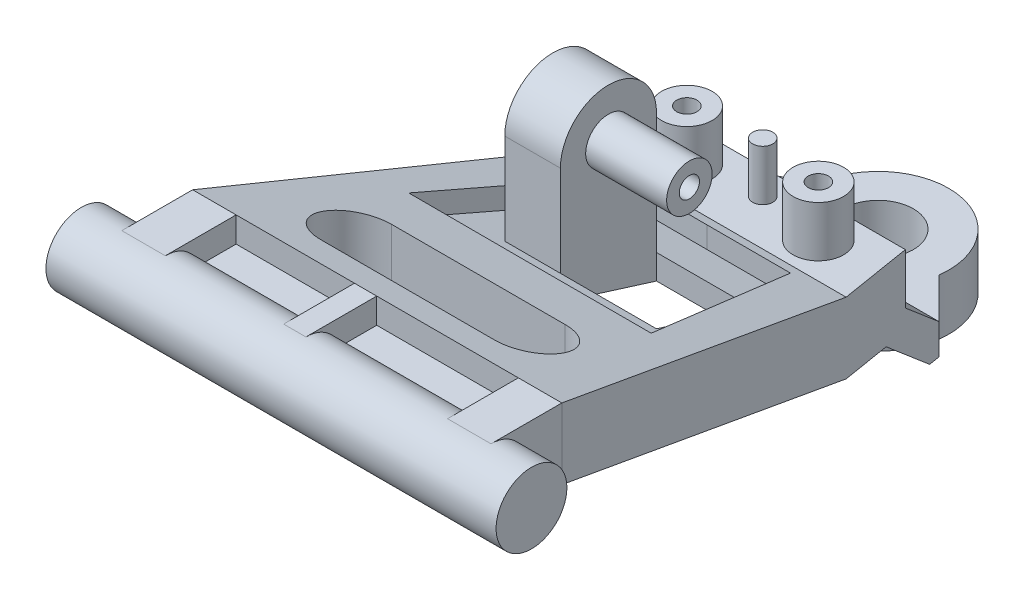
SolidWorks part; units mm, degrees
note: The reader was unsure of these and kept them because the rebuilt part matched: shared geometry of "Sketch13<3>", "Sketch13<4>".
ref_plane "Front Plane" through (0, 0, 0) normal (0, 0, 1) x (1, 0, 0)
ref_plane "Top Plane" through (0, 0, 0) normal (0, 1, 0) x (1, 0, 0)
ref_plane "Right Plane" through (0, 0, 0) normal (1, 0, 0) x (0, 0, -1)
sketch "Sketch1" plane through (0, 0, 0) normal (1, 0, 0) x (0, 0, -1)
  line L0 (7, -3.5) -> (40.6071, -14)
  line L1 (40.6071, -14) -> (45.75, -18.5)
  line L2 (45.75, -18.5) -> (49.75, -18.5)
  line L4 (49.75, -18.5) -> (63.5, -18.5)
  line L5 (63.5, -18.5) -> (63.5, -15.5)
  line L6 (63.5, -15.5) -> (51.6071, -15.5)
  line L7 (51.6071, -15.5) -> (47.6071, -12)
  line L8 (47.6071, -12) -> (47.6071, -7)
  line L9 (47.6071, -7) -> (40.6071, -7)
  line L10 (40.6071, -7) -> (7, 3.5)
  line L11 (0, 3.5) -> (7, 3.5)
  line L12 (0, -3.5) -> (7, -3.5)
  arc A0 (0, 3.5) -> (0, -3.5) centre (0, 0) ccw
  dimension "D1" = 7
  dimension "D2" = 5
  dimension "D7" = 63.5
  dimension "D4" = 18.5
  dimension "D3" = 13.75
  dimension "D5" = 3
  dimension "D6" = 4
  dimension "D9" = 7
  dimension "D10" = 7
  dimension "D11" = 7
  dimension "D12" = 4
extrude "Boss-Extrude1" add sketch "Sketch1" along normal blind 36.5 contours L10 L11 A0 L12 L0 L1 L2 L4 L5 L6 L7 L8 L9
sketch "Sketch2" plane through (0, 0, 0) normal (0, 1, 0) x (1, 0, 0)
  line L0 (18.25, -3.5) -> (18.25, 63.5) construction
  line L1 (0, -3.5) -> (36.5, -3.5) construction
  line L2 (36.5, 63.5) -> (36.5, 51.6071) construction
  line L3 (25.1928, 55.6071) -> (29.1928, 51.6071)
  line L4 (36.5, 51.6071) -> (0, 51.6071) construction
  line L5 (29.1928, 51.6071) -> (36.5, 7)
  line L6 (36.5, 7) -> (46.5, 7)
  line L7 (46.5, 7) -> (46.5, 73.5)
  line L8 (46.5, 73.5) -> (-10, 73.5)
  line L9 (-10, 7) -> (-10, 73.5)
  line L10 (0, 7) -> (-10, 7)
  line L11 (7.9624, 55.6071) -> (0, 7)
  line L12 (11.3381, 57.6071) -> (7.9624, 55.6071)
  line L13 (36.5, 63.5) -> (0, 63.5) construction
  line L14 (9.6781, 13.5) -> (26.8219, 13.5) construction
  line L15 (9.6781, 17) -> (26.8219, 17)
  line L16 (9.6781, 10) -> (26.8219, 10)
  line L17 (36.5, 7) -> (0, 7) construction
  line L18 (36.5, 47.6071) -> (0, 47.6071) construction
  line L19 (17.25, 35.6071) -> (26.75, 35.6071)
  line L20 (17.25, 35.6071) -> (17.25, 26.1071)
  line L21 (17.25, 26.1071) -> (26.75, 26.1071)
  line L22 (26.75, 35.6071) -> (26.75, 26.1071)
  arc A0 (25.1928, 55.6071) -> (11.3381, 57.6071) centre (18.25, 56.5) ccw
  circle A1 centre (18.25, 56.5) radius 3.5
  arc A2 (9.6781, 17) -> (9.6781, 10) centre (9.6781, 13.5) ccw
  arc A3 (26.8219, 10) -> (26.8219, 17) centre (26.8219, 13.5) ccw
  point P20 (18.25, 73.5)
  point P23 (18.25, 13.5)
  dimension "D1" = 14
  dimension "D8" = 7
  dimension "D9" = 3.5
  dimension "D2" = 4
  dimension "D3" = 4
  dimension "D4" = 9.303
  dimension "D5" = 2
  dimension "D6" = 10
  dimension "D7" = 10
  dimension "D10" = 8.5
  dimension "D11" = 3
  dimension "D12" = 1
  dimension "D13" = 12
  dimension "D14" = 9.5
  dimension "D15" = 9.5
extrude "Cut-Extrude1" cut sketch "Sketch2" against normal blind 36.5 and the other way through all
sketch "Sketch5" plane through (0, 3.5, 0) normal (0, 1, 0) x (1, 0, 0)
  line L0 (36.5, 0) -> (0, 0) construction
  line L1 (4.3, 0) -> (16, 0)
  line L2 (4.3, 0) -> (4.3, 7)
  line L3 (4.3, 7) -> (16, 7)
  line L4 (16, 0) -> (16, 7)
  line L5 (36.5, 0) -> (36.5, 7) construction
  line L6 (18.2, 7) -> (32.2, 7)
  line L7 (18.2, 7) -> (18.2, 0)
  line L8 (18.2, 0) -> (32.2, 0)
  line L9 (32.2, 7) -> (32.2, 0)
  line L10 (0, 0) -> (0, 7) construction
  line L12 (9.6781, 10) -> (26.8219, 10) construction
  dimension "D1" = 4.3
  dimension "D2" = 4.3
  dimension "D3" = 3
  dimension "D4" = 2.2
  dimension "D5" = 14
extrude "Cut-Extrude2" cut sketch "Sketch5" against normal blind 2.5
sketch "Sketch6" plane through (0, -3.5, 0) normal (0, -1, 0) x (1, 0, 0)
  line L4 (18.2, -7) -> (32.2, -7)
  line L5 (32.2, -7) -> (32.2, 0)
  line L6 (32.2, 0) -> (18.2, 0)
  line L7 (18.2, 0) -> (18.2, -7)
  line L8 (18.2, -7) -> (32.2, -7)
  line L9 (32.2, -7) -> (32.2, 0)
  line L10 (32.2, 0) -> (18.2, 0)
  line L11 (18.2, 0) -> (18.2, -7)
  line L12 (16, 0) -> (4.3, 0)
  line L13 (16, -7) -> (16, 0)
  line L14 (4.3, -7) -> (16, -7)
  line L15 (4.3, 0) -> (4.3, -7)
  line L16 (16, 0) -> (4.3, 0)
  line L17 (16, -7) -> (16, 0)
  line L18 (4.3, -7) -> (16, -7)
  line L19 (4.3, 0) -> (4.3, -7)
  dimension "D1" = 0
  dimension "D2" = 0
extrude "Cut-Extrude3" cut sketch "Sketch6" against normal blind 2.5
sketch "Sketch3" plane through (36.5, 0, 0) normal (1, 0, 0) x (0, 0, -1)
  circle A0 centre (0, 0) radius 3.5
  dimension "D1" = 7
extrude "Boss-Extrude2" add sketch "Sketch3" along normal blind 4 and the other way blind 40.5 contours A0
sketch "Sketch7" plane through (0, 0, 0) normal (0, 1, 0) x (1, 0, 0)
  line L0 (18.2225, 22.1071) -> (30.2225, 22.1071)
  line L1 (30.2225, 22.1071) -> (26.4985, 39.6071)
  line L2 (26.4985, 39.6071) -> (18.2485, 39.6071)
  line L4 (18.2, 7) -> (18.25, 40.6071) construction
  line L5 (30.9948, 40.6071) -> (5.5052, 40.6071) construction
  line L6 (9.9985, 39.6317) -> (18.2485, 39.6071)
  line L7 (6.2225, 22.1428) -> (9.9985, 39.6317)
  line L8 (18.2225, 22.1071) -> (6.2225, 22.1428)
  dimension "D1" = 8.25
  dimension "D2" = 12
  dimension "D3" = 17.5
  dimension "D4" = 1
extrude "Cut-Extrude4" cut sketch "Sketch7" against normal offset from surface (8.8061 mm away) 4.6667
ref_plane "Plane1" through (0, -18.5, 0) normal (0, 1, 0) x (1, 0, 0)
sketch "Sketch8" plane through (0, -18.5, 0) normal (0, 1, 0) x (1, 0, 0)
  line L6 (18.2225, 22.1071) -> (30.2225, 22.1071)
  line L7 (30.2225, 22.1071) -> (26.4985, 39.6071)
  line L8 (26.4985, 39.6071) -> (18.2485, 39.6071)
  line L9 (18.2485, 39.6071) -> (9.9985, 39.6317)
  line L10 (9.9985, 39.6317) -> (6.2225, 22.1428)
  line L11 (6.2225, 22.1428) -> (18.2225, 22.1071)
  line L12 (18.2225, 22.1071) -> (30.2225, 22.1071)
  line L13 (30.2225, 22.1071) -> (26.4985, 39.6071)
  line L14 (26.4985, 39.6071) -> (18.2485, 39.6071)
  line L15 (18.2485, 39.6071) -> (9.9985, 39.6317)
  line L16 (9.9985, 39.6317) -> (6.2225, 22.1428)
  line L17 (6.2225, 22.1428) -> (18.2225, 22.1071)
  dimension "D1" = 0
extrude "Cut-Extrude5" cut sketch "Sketch8" along normal offset from surface (7.2493 mm away) 2.3333
sketch "Sketch9" plane through (17.25, 0, 0) normal (1, 0, 0) x (0, 0, -1)
  line L0 (26.1071, -4.5806) -> (26.1071, 4.4194)
  line L1 (35.6071, 4.4194) -> (35.6071, -7.5487)
  line L2 (26.1071, -4.5806) -> (35.6071, -7.5487)
  line L3 (35.6071, -7.5487) -> (26.1071, -4.5806) construction
  arc A0 (26.1071, 4.4194) -> (35.6071, 4.4194) centre (30.8571, 4.4194) cw
  dimension "D1" = 9
extrude "Boss-Extrude3" add sketch "Sketch9" against normal blind 5.5
sketch "Sketch10" plane through (17.25, 0, 0) normal (1, 0, 0) x (0, 0, -1)
  circle A0 centre (30.8571, 4.4194) radius 2.25
  circle A1 centre (30.8571, 4.4194) radius 1
  dimension "D1" = 4.5
  dimension "D2" = 2
extrude "Boss-Extrude4" add sketch "Sketch10" along normal blind 8
sketch "Sketch11" plane through (0, -7, 0) normal (0, 1, 0) x (1, 0, 0)
  line L0 (18.25, 47.6071) -> (18.25, 40.6071) construction
  line L1 (29.8481, 47.6071) -> (6.6519, 47.6071) construction
  line L2 (30.9948, 40.6071) -> (5.5052, 40.6071) construction
  line L3 (29.8481, 47.6071) -> (6.6519, 47.6071) construction
  line L4 (11.75, 44.1071) -> (18.25, 44.1071) construction
  circle A0 centre (11.75, 44.1071) radius 2.5
  circle A1 centre (18.25, 45.1071) radius 1
  circle A2 centre (11.75, 44.1071) radius 1
  circle A3 centre (24.75, 44.1071) radius 1
  circle A4 centre (24.75, 44.1071) radius 2.5
  dimension "D1" = 2
  dimension "D2" = 5
  dimension "D3" = 2.5
  dimension "D5" = 2
  dimension "D4" = 6.5
extrude "Boss-Extrude5" add sketch "Sketch11" along normal blind 5
sketch "Sketch13" plane through (0, 0, 0) normal (1, 0, 0) x (0, 0, -1)
  line L0 (51.6071, -15.5) -> (47.6071, -12) construction
  line L1 (55.6071, -15.5) -> (51.6071, -15.5) construction
  line L2 (51.6071, -15.5) -> (47.6071, -12) construction
  line L3 (55.6071, -15.5) -> (51.6071, -15.5) construction
  line L5 (53.9085, -21.5) -> (45.3371, -14)
  line L6 (45.75, -18.5) -> (51.6071, -18.5) construction
  line L7 (40.6071, -14) -> (45.3371, -14)
  line L8 (40.6071, -14) -> (40.6071, -21.5)
  line L9 (40.6071, -21.5) -> (53.9085, -21.5)
  dimension "D2" = 3
  dimension "D1" = 3
extrude "Cut-Extrude7" cut sketch "Sketch13" along normal blind 12 contours L9 L5 L7 L8
extrude "Cut-Extrude8" cut sketch "Sketch13<3>" along normal blind 8.25 from offset 14.5
sketch "Sketch13<3>" plane through (0, 0, 0) normal (1, 0, 0) x (0, 0, -1) same geometry as "Sketch13"
extrude "Cut-Extrude9" cut sketch "Sketch13<4>" along normal blind 8 from offset 25.25
sketch "Sketch13<4>" plane through (0, 0, 0) normal (1, 0, 0) x (0, 0, -1) same geometry as "Sketch13"
sketch "Sketch14" plane through (0, -18.5, 0) normal (0, -1, 0) x (1, 0, 0)
  circle A0 centre (18.25, -56.5) radius 7
  circle A1 centre (18.25, -56.5) radius 3.5
  dimension "D1" = 14
  dimension "D2" = 7
extrude "Boss-Extrude6" add sketch "Sketch14" along normal blind 2.5 and the other way up to surface other way up to face at (27.5244, -16.25, -47.9085)
